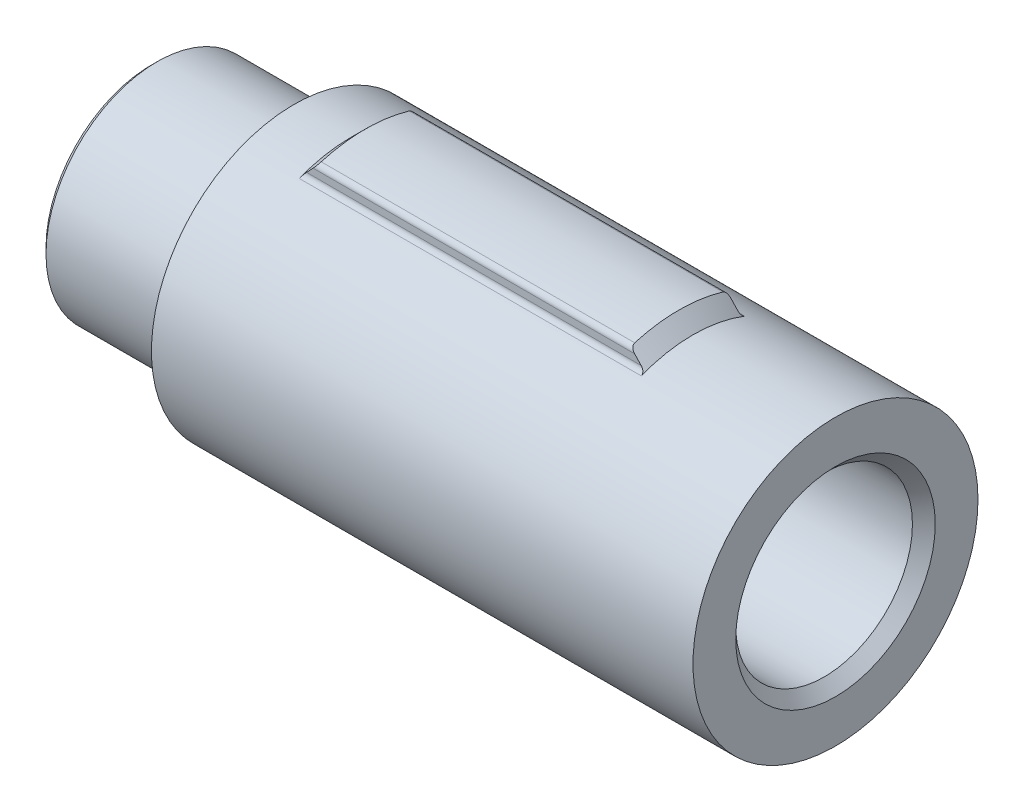
SolidWorks part; units mm, degrees
ref_plane "前视基准面" through (0, 0, 0) normal (0, 0, 1) x (1, 0, 0)
ref_plane "上视基准面" through (0, 0, 0) normal (0, 1, 0) x (1, 0, 0)
ref_plane "右视基准面" through (0, 0, 0) normal (1, 0, 0) x (0, 0, -1)
other "Configuration Table"
sketch "草图1" plane through (0, 0, 0) normal (1, 0, 0) x (0, 0, -1)
  circle A0 centre (0, 0) radius 5
  dimension "D1" = 10
extrude "凸台-拉伸1" add sketch "草图1" along normal blind 19
sketch "草图3" plane through (19, 0, 0) normal (1, 0, 0) x (0, 0, -1)
  circle A0 centre (0, 0) radius 3.1
  dimension "D1" = 6.2
extrude "切除-拉伸1" cut sketch "草图3" against normal blind 17
sketch "草图5" plane through (2, 0, 0) normal (1, 0, 0) x (0, 0, -1)
  line L1 (-1.6882, 2.6) -> (1.6882, 2.6)
  line L2 (-1.6882, 2.6) -> (-1.6882, 5.2345)
  line L3 (1.6882, 2.6) -> (1.6882, 5.2345)
  line L4 (0, 5.5) -> (1.6882, 5.5) construction
  line L5 (-1.6882, 5.5) -> (0, 5.5) construction
  line L6 (-1.6882, 5.2345) -> (-1.6882, 5.5) construction
  line L7 (1.6882, 5.2345) -> (1.6882, 5.5) construction
  circle A0 centre (0, 0) radius 3.1 construction
  arc A1 (1.6882, 2.6) -> (-1.6882, 2.6) centre (0, 0) ccw construction
  arc A2 (-1.6882, 2.6) -> (1.6882, 2.6) centre (0, 0) ccw construction
  arc A5 (-1.6882, 5.2345) -> (1.6882, 5.2345) centre (0, 0) ccw construction
  circle A6 centre (0, 0) radius 5.5
  arc A7 (1.6882, 5.2345) -> (-1.6882, 5.2345) centre (0, 0) ccw
  dimension "D1" = 2.6
  dimension "D2" = 0.5
extrude "凸台-拉伸2" add sketch "草图5" along normal blind 12
sketch "草图8" plane through (0, 0, 0) normal (-1, 0, 0) x (0, 0, 1)
  circle A0 centre (0, 0) radius 3.9
  dimension "D1" = 7.8
extrude "凸台-拉伸4" add sketch "草图8" along normal blind 5
sketch "草图9" plane through (-5, 0, 0) normal (-1, 0, 0) x (0, 0, 1)
  circle A0 centre (0, 0) radius 2.8
  dimension "D1" = 5.6
extrude "切除-拉伸2" cut sketch "草图9" against normal blind 5
sketch "草图10" plane through (0, 0, 0) normal (-1, 0, 0) x (0, 0, 1)
  line L1 (0.6928, 1.2) -> (-0.6928, 1.2)
  line L2 (-0.6928, 1.2) -> (-1.3856, 0)
  line L3 (-1.3856, 0) -> (-0.6928, -1.2)
  line L4 (-0.6928, -1.2) -> (0.6928, -1.2)
  line L5 (0.6928, -1.2) -> (1.3856, 0)
  line L6 (1.3856, 0) -> (0.6928, 1.2)
  circle A0 centre (0, 0) radius 1.2 construction
  dimension "D1" = 2.4
extrude "凸台-拉伸5" add sketch "草图10" along normal blind 3.2
fillet "圆角1" radius 0.2 4 edges at (8, 4.7064, -1.6882) (8, 5.2345, -1.6882) (8, 4.7064, 1.6882) (8, 5.2345, 1.6882)
chamfer "倒角1" distance 0.5 angle 45 3 edges at (14, 5.5, 0) (2, 5.5, 0) (14, 2.6, 0)
chamfer "倒角2" distance 0.4 angle 45 1 edges at (19, 0, -3.1)
chamfer "倒角3" distance 0.2 angle 45 8 edges at (-3.2, -0.6, 1.0392) (-3.2, -1.2, 0) (-3.2, -0.6, -1.0392) (-3.2, 0.6, -1.0392) (-3.2, 1.2, 0) (-3.2, 0.6, 1.0392) (-5, 0, 3.9) (-5, 0, 2.8)
